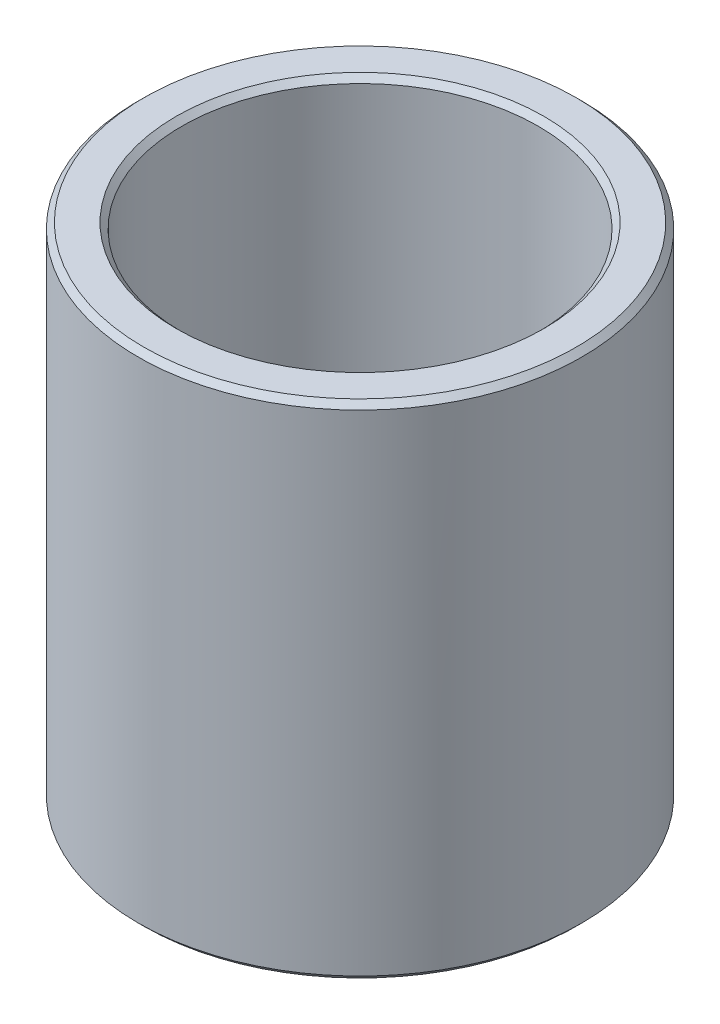
SolidWorks part; units mm, degrees
ref_plane "Front Plane" through (0, 0, 0) normal (0, 0, 1) x (1, 0, 0)
ref_plane "Top Plane" through (0, 0, 0) normal (0, 1, 0) x (1, 0, 0)
ref_plane "Right Plane" through (0, 0, 0) normal (1, 0, 0) x (0, 0, -1)
sketch "Sketch1" plane through (0, 0, 0) normal (0, 1, 0) x (1, 0, 0)
  circle A0 centre (0, 0) radius 15
  dimension "SLEEVE_OD" = 30
extrude "Boss-Extrude1" add sketch "Sketch1" along normal blind 33.9125
sketch "Sketch2" plane through (0, 0, 0) normal (0, 1, 0) x (1, 0, 0)
  circle A0 centre (0, 0) radius 12.0494
  dimension "BORE_D" = 24.0988
extrude "Cut-Extrude1" cut sketch "Sketch2" along normal through all
chamfer "Chamfer1" distance 0.3849 angle 45 4 edges at (0, 33.9125, 12.0494) (0, 0, 12.0494) (0, 0, 15) (0, 33.9125, 15)
